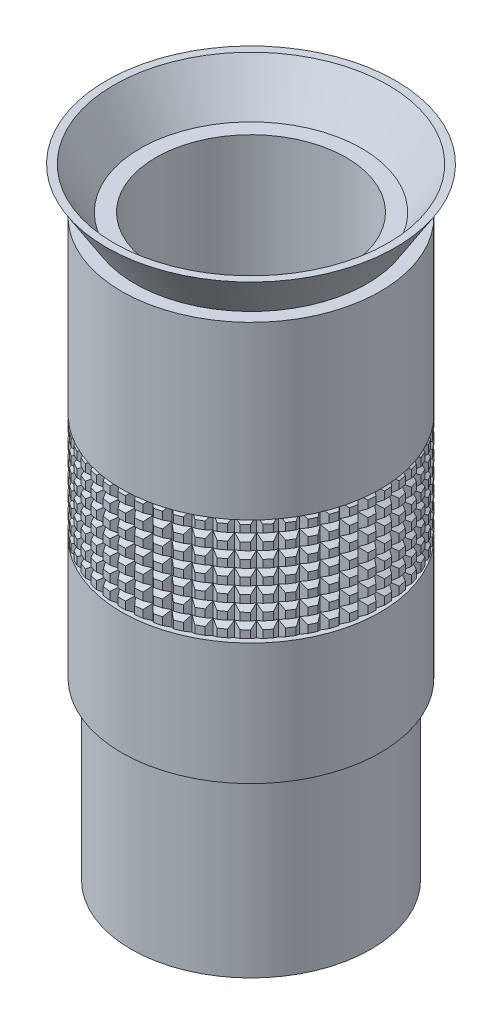
SolidWorks part; units mm, degrees
ref_plane "Plan de face" through (0, 0, 0) normal (0, 0, 1) x (1, 0, 0)
ref_plane "Plan de dessus" through (0, 0, 0) normal (0, 1, 0) x (1, 0, 0)
ref_plane "Plan de droite" through (0, 0, 0) normal (1, 0, 0) x (0, 0, -1)
sketch "Esquisse1" plane through (0, 0, 0) normal (0, 0, 1) x (1, 0, 0)
  line L0 (0, 0) -> (0, 66.529) construction
  line L1 (13.75, 0) -> (13.75, 20)
  line L2 (13.75, 0) -> (15.75, 0)
  line L3 (15.75, 0) -> (15.75, 23)
  line L4 (15.75, 23) -> (17, 23)
  line L5 (17, 23) -> (17, 39)
  line L6 (17, 75.5) -> (15.25, 75.5)
  line L7 (15.25, 75.5) -> (19, 81.5)
  line L8 (19, 81.5) -> (18, 81.5)
  line L9 (18, 81.5) -> (14.5625, 76)
  line L10 (14.5625, 76) -> (12.5, 76)
  line L11 (12.5, 76) -> (12.5, 20)
  line L12 (12.5, 20) -> (13.75, 20)
  line L13 (17, 39) -> (16.2, 39)
  line L15 (17, 52.5) -> (16.2, 53)
  line L16 (8.0154, 46) -> (29.7633, 46) construction
  line L17 (17, 53) -> (17, 75.5)
  line L18 (17, 39.5) -> (17, 40.5)
  line L19 (17, 41.5) -> (17, 42.5)
  line L20 (17, 43.5) -> (17, 44.5)
  line L21 (16.2, 45) -> (17, 45.5)
  line L22 (16.2, 45) -> (17, 44.5)
  line L23 (17, 43.5) -> (16.2, 43)
  line L24 (16.2, 43) -> (17, 42.5)
  line L25 (17, 41.5) -> (16.2, 41)
  line L26 (17, 40.5) -> (16.2, 41)
  line L27 (17, 45.5) -> (17, 46.5)
  line L28 (17, 39.5) -> (16.2, 39)
  line L29 (17, 53) -> (16.2, 53)
  line L30 (16.2, 51) -> (17, 51.5)
  line L31 (17, 50.5) -> (16.2, 51)
  line L32 (16.2, 49) -> (17, 49.5)
  line L33 (17, 48.5) -> (16.2, 49)
  line L34 (16.2, 47) -> (17, 47.5)
  line L35 (16.2, 47) -> (17, 46.5)
  line L36 (17, 48.5) -> (17, 47.5)
  line L37 (17, 50.5) -> (17, 49.5)
  line L38 (17, 52.5) -> (17, 51.5)
  point P34 (17, 46)
  dimension "D1" = 31.5
  dimension "D2" = 27.5
  dimension "D3" = 20
  dimension "D4" = 25
  dimension "D5" = 23
  dimension "D6" = 34
  dimension "D7" = 52.5
  dimension "D8" = 30.5
  dimension "D9" = 6
  dimension "D10" = 38
  dimension "D11" = 1
  dimension "D12" = 5.5
  dimension "D13" = 16
  dimension "D16" = 7
revolve "Révolution1" add sketch "Esquisse1" angle 360 about L0
sketch "Esquisse2" plane through (0, 53, 0) normal (0, -1, 0) x (1, 0, 0)
  line L0 (0, 0) -> (0, 22.0388) construction
  line L1 (0, 0) -> (-0.623, 21.1744) construction
  line L2 (0, 0) -> (-1.2479, 19.835) construction
  line L3 (0, 0) -> (0.623, 21.1744) construction
  line L4 (0, 0) -> (1.2512, 19.8874) construction
  line L5 (-0.5, 16.9926) -> (-1.0172, 16.168)
  line L6 (0.5, 16.9926) -> (1.0172, 16.168)
  line L7 (-1.0172, 16.168) -> (-1.8393, 21.962)
  line L8 (1.0172, 16.168) -> (2.1461, 21.9341)
  circle A0 centre (0, 0) radius 17 construction
  arc A1 (0.5, 16.9926) -> (-0.5, 16.9926) centre (0, 0) ccw
  arc A2 (2.1461, 21.9341) -> (-1.8393, 21.962) centre (0, 0) ccw
  dimension "D1" = 7.2
  dimension "D2" = 3.6
extrude "Enlèv. mat.-Extru.1" cut sketch "Esquisse2" along normal blind 14
pattern_circular "Répétition circulaire1" count 50 over 360 about axis through (0, 0, 0) along (0, -1, 0) of "Enlèv. mat.-Extru.1"
